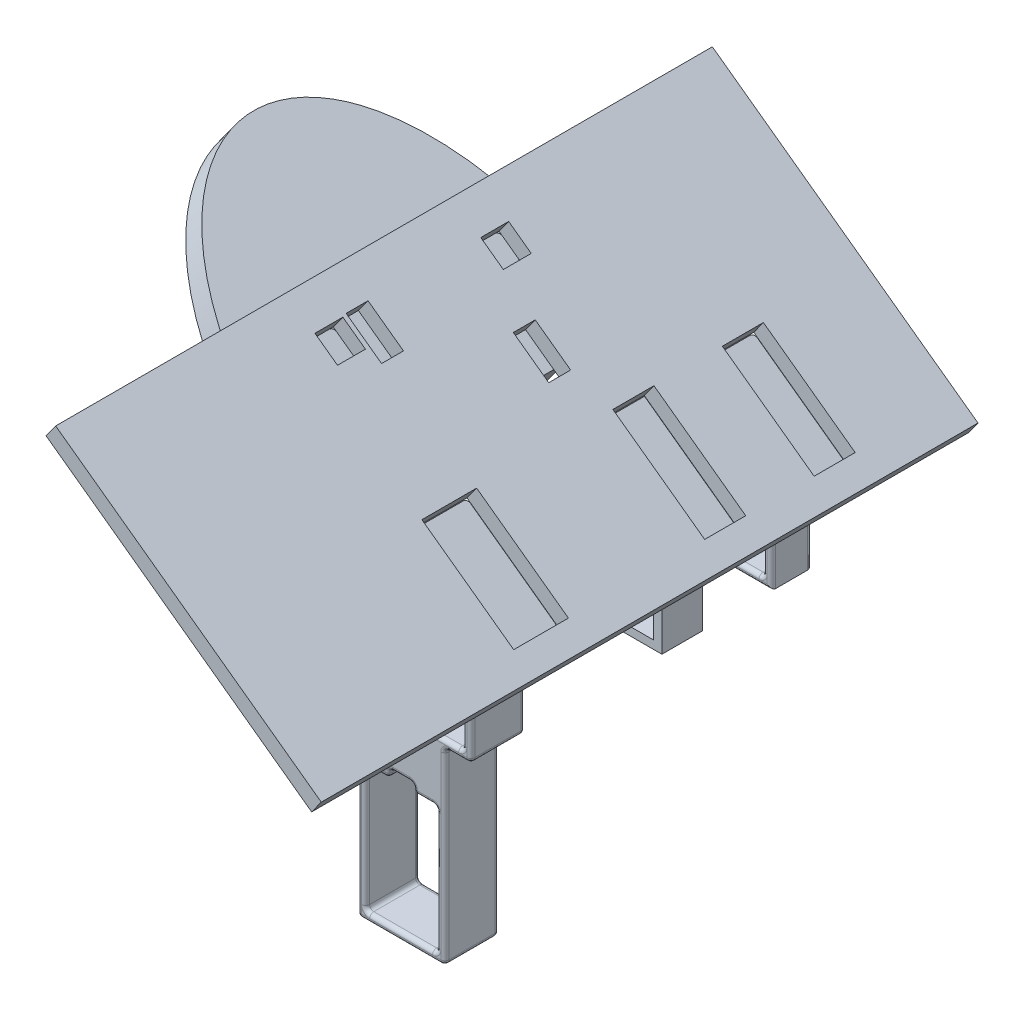
SolidWorks part; units mm, degrees
note: The reader was unsure of these and kept them because the rebuilt part matched: shared geometry of "Sketch7<2>".
ref_plane "Front Plane" through (0, 0, 0) normal (0, 0, 1) x (1, 0, 0)
ref_plane "Top Plane" through (0, 0, 0) normal (0, 1, 0) x (1, 0, 0)
ref_plane "Right Plane" through (0, 0, 0) normal (1, 0, 0) x (0, 0, -1)
sketch "Sketch3" plane through (0, 0, 0) normal (0, 0, 1) x (1, 0, 0)
  line L0 (-12.75, 5.65) -> (12.75, 5.65) construction
  line L1 (-11.25, -4.15) -> (11.25, -4.15)
  line L2 (-11.25, -4.15) -> (-11.25, 4.15)
  line L3 (-11.25, 4.15) -> (11.25, 4.15)
  line L4 (11.25, -4.15) -> (11.25, 4.15)
  line L5 (-11.25, -4.15) -> (11.25, 4.15) construction
  line L6 (-11.25, 4.15) -> (11.25, -4.15) construction
  line L7 (-6.5, -15.45) -> (6.5, -15.45) construction
  line L8 (-6.5, -15.45) -> (-6.5, -38.55)
  line L9 (-6.5, -38.55) -> (6.5, -38.55)
  line L10 (6.5, -15.45) -> (6.5, -38.55)
  line L11 (-6.5, -15.45) -> (6.5, -38.55) construction
  line L12 (-6.5, -38.55) -> (6.5, -15.45) construction
  line L13 (12.75, -5.65) -> (12.75, 5.65)
  line L15 (-12.75, -5.65) -> (-12.75, 5.65)
  line L16 (8, -13.95) -> (8, -40.05)
  line L17 (-8, -40.05) -> (8, -40.05)
  line L18 (-8, -13.95) -> (-8, -40.05)
  line L20 (-8, -13.95) -> (8, -13.95) construction
  line L21 (-12.75, -5.65) -> (12.75, -5.65) construction
  line L22 (-8, -13.95) -> (-8, -5.65)
  line L23 (-8, -5.65) -> (-12.75, -5.65)
  line L24 (12.75, -5.65) -> (8, -5.65)
  line L25 (8, -5.65) -> (8, -13.95)
  line L26 (-12.75, 5.65) -> (2.1671, 26.1817)
  line L27 (2.1671, 26.1817) -> (18.8571, 14.0557)
  line L28 (18.8571, 14.0557) -> (12.75, 5.65)
  line L29 (0, -40.05) -> (0, 5.65) construction
  line L30 (-6.5, -15.45) -> (-2.25, -15.45)
  line L31 (-2.25, -15.45) -> (-2.25, -13.95)
  line L32 (-2.25, -13.95) -> (2.25, -13.95)
  line L33 (2.25, -13.95) -> (2.25, -15.45)
  line L34 (2.25, -15.45) -> (6.5, -15.45)
  point P0 (0, 0)
  point P5 (0, -27)
  point P28 (0, -13.95)
  dimension "D1" = 22.5
  dimension "D2" = 1.5
  dimension "D3" = 27
  dimension "D4" = 13
  dimension "D5" = 23.1
  dimension "D7" = 1.5
  dimension "D8" = 54
  dimension "D9" = 10.39
  dimension "D10" = 8.4057
  dimension "D11" = 16
  dimension "D12" = 4.5
  dimension "D13" = 1.5
  dimension "D14" = 8.3
  dimension "D6" = 11.3
  dimension "D15" = 20.6299
extrude "Boss-Extrude1" add sketch "Sketch3" along normal blind 9.9
sketch "Sketch4" plane through (13.1988, 18.1666, 0) normal (0.5878, 0.809, 0) x (0.809, -0.5878, 0)
  line L0 (-3.321, 0) -> (-3.321, -9.9) construction
  line L1 (6.994, 0) -> (-13.636, 0) construction
  line L2 (6.994, -9.9) -> (-13.636, -9.9) construction
  line L3 (-13.636, -4.95) -> (6.994, -4.95) construction
  line L4 (-13.636, -9.9) -> (-13.636, 0) construction
  line L5 (6.994, -9.9) -> (6.994, 0) construction
  line L7 (-48.321, 71.1) -> (11.679, 71.1)
  line L8 (-48.321, 71.1) -> (-48.321, -48.9)
  line L9 (-48.321, -48.9) -> (11.679, -48.9)
  line L10 (11.679, 71.1) -> (11.679, -48.9)
  line L11 (-48.321, 71.1) -> (11.679, -48.9) construction
  line L12 (-48.321, -48.9) -> (11.679, 71.1) construction
  point P12 (-3.321, -4.95)
  point P13 (-18.321, 11.1)
  dimension "D1" = 120
  dimension "D2" = 60
  dimension "D3" = 16.05
  dimension "D4" = 15
extrude "Boss-Extrude2" add sketch "Sketch4" along normal blind 3
sketch "Sketch7" plane through (13.1988, 18.1666, 0) normal (-0.5878, -0.809, 0) x (0.809, -0.5878, 0)
  line L0 (-14.9179, -11.1) -> (-63.9179, -11.1) construction
  line L1 (-48.321, 48.9) -> (11.679, 48.9) construction
  line L6 (-36.7569, 1.65) -> (-41.8569, 1.65)
  line L7 (-36.7569, 1.65) -> (-36.7569, 6.75)
  line L8 (-36.7569, 6.75) -> (-41.8569, 6.75)
  line L9 (-41.8569, 1.65) -> (-41.8569, 6.75)
  line L10 (-36.7569, 1.65) -> (-41.8569, 6.75) construction
  line L11 (-36.7569, 6.75) -> (-41.8569, 1.65) construction
  line L12 (-48.321, -71.1) -> (-48.321, 48.9) construction
  line L13 (-36.7569, -23.55) -> (-36.7569, -28.65)
  line L14 (-36.7569, -23.55) -> (-41.8569, -23.55)
  line L15 (-41.8569, -23.55) -> (-41.8569, -28.65)
  line L16 (-36.7569, -28.65) -> (-41.8569, -28.65)
  line L17 (-41.8569, -23.55) -> (-36.7569, -28.65) construction
  point P10 (-39.3069, -26.1)
  point P11 (-39.3069, 4.2)
  point P12 (0, 0)
  point P13 (-36.7569, -28.65)
  point P18 (0, 0)
  point P19 (0, 0)
  point P20 (0, 0)
  point P21 (0, 0)
  dimension "D1" = 6.4641
  dimension "D3" = 5.1
  dimension "D4" = 5.1
  dimension "D5" = 5.1
  dimension "D6" = 6.4641
  dimension "D7" = 12.45
  dimension "D8" = 60
  dimension "D9" = 30.3
extrude "Boss-Extrude3" add sketch "Sketch7" along normal blind 4.5 and the other way blind 3
sketch "Sketch8" plane through (10.5538, 14.5261, 0) normal (-0.5878, -0.809, 0) x (0.809, -0.5878, 0)
  line L2 (-23.3069, 5.8504) -> (-23.3069, -28.0504)
  line L3 (-23.3069, 5.8504) -> (-34.6206, 17.1641)
  line L4 (-23.3069, -28.0504) -> (-34.6206, -39.3641)
  line L6 (11.679, -71.1) -> (-48.321, -71.1) construction
  line L7 (-48.321, 48.9) -> (11.679, -71.1) construction
  line L8 (-18.321, -11.1) -> (-48.321, -11.1) construction
  line L9 (11.679, 48.9) -> (11.679, -71.1) construction
  ellipse E0 centre (-23.3069, -11.1) end of major axis (-72.2778, -11.1) minor radius 29.05 (-34.6206, 17.1641) -> (-34.6206, -39.3641) ccw
  dimension "D1" = 4.9859
  dimension "D2" = 28.2641
  dimension "D3" = 23.9569
  dimension "D4" = 45
  dimension "D5" = 16
  dimension "D6" = 48.9709
  dimension "D7" = 60
  dimension "D8" = 34.9859
extrude "Boss-Extrude4" add sketch "Sketch8" along normal blind 5
ref_plane "Plane1" through (0, 0, -25) normal (0, 0, -1) x (-1, 0, 0)
ref_plane "Plane2" through (0, 0, -45) normal (0, 0, -1) x (-1, 0, 0)
sketch "Sketch9" plane through (0, 0, -25) normal (0, 0, -1) x (-1, 0, 0)
  line L0 (-20.6204, 16.4827) -> (-12.75, 5.65)
  line L2 (-3.9305, 28.6087) -> (12.75, 5.65)
  line L3 (12.75, 5.65) -> (12.75, -5.65)
  line L4 (12.75, -5.65) -> (8, -5.65)
  line L5 (8, -5.65) -> (-12.75, -5.65)
  line L6 (-12.75, -5.65) -> (-12.75, 5.65)
  line L7 (-11.25, 4.15) -> (11.25, 4.15)
  line L8 (11.25, 4.15) -> (11.25, -4.15)
  line L9 (11.25, -4.15) -> (-11.25, -4.15)
  line L10 (-11.25, -4.15) -> (-11.25, 4.15)
  line L12 (-24.4107, 13.7289) -> (-22.6474, 11.3019) construction
  line L13 (-24.4107, 13.7289) -> (24.1303, 48.9961) construction
  line L14 (-20.6204, 16.4827) -> (-3.9305, 28.6087)
  dimension "D1" = 4.685
extrude "Boss-Extrude5" add sketch "Sketch9" along normal blind 7.4 contours L10 L9 L8 L7 | L0 L6 L5 L4 L3 L2 L14
sketch "Sketch10" plane through (0, 0, -45) normal (0, 0, -1) x (-1, 0, 0)
  line L0 (-20.6204, 16.4827) -> (-12.75, 5.65)
  line L1 (-20.6204, 16.4827) -> (-3.9305, 28.6087)
  line L2 (-3.9305, 28.6087) -> (12.75, 5.65)
  line L3 (12.75, 5.65) -> (12.75, -5.65)
  line L6 (-12.75, -5.65) -> (-12.75, 5.65)
  line L7 (-11.25, 4.15) -> (11.25, 4.15)
  line L8 (11.25, 4.15) -> (11.25, -4.15)
  line L9 (11.25, -4.15) -> (-11.25, -4.15)
  line L10 (-11.25, -4.15) -> (-11.25, 4.15)
  line L11 (-24.4107, 13.7289) -> (24.1303, 48.9961) construction
  line L13 (-18.8571, 14.0557) -> (-12.75, 5.65) construction
  line L14 (-12.75, -5.65) -> (-12.75, 5.65) construction
  line L16 (-2.1671, 26.1817) -> (12.75, 5.65) construction
  line L17 (12.75, 5.65) -> (12.75, -5.65) construction
  line L18 (-12.75, -5.65) -> (12.75, -5.65)
extrude "Boss-Extrude6" add sketch "Sketch10" along normal blind 7.4
sketch "Sketch11" plane through (13.1988, 18.1666, 0) normal (-0.5878, -0.809, 0) x (0.809, -0.5878, 0)
  line L0 (-13.636, 9.9) -> (-13.636, 0) construction
  line L9 (6.994, 9.9) -> (6.994, 0) construction
  line L10 (-48.321, 48.9) -> (11.679, 48.9) construction
  line L11 (-13.636, -32.4) -> (-13.636, -25) construction
  line L12 (11.679, 48.9) -> (11.679, -71.1) construction
  line L13 (6.994, 9.9) -> (-13.636, 9.9) construction
  line L24 (-13.741, 9.95) -> (6.989, 9.95)
  line L25 (-13.741, 9.95) -> (-13.741, -0.05)
  line L26 (-13.741, -0.05) -> (6.989, -0.05)
  line L27 (6.989, 9.95) -> (6.989, -0.05)
  line L28 (-37.611, 48.9) -> (-37.611, -71.1) construction
  line L29 (6.994, 0) -> (-13.636, 0) construction
  line L30 (-13.741, -24.95) -> (6.989, -24.95)
  line L35 (-13.741, -24.95) -> (-13.741, -32.45)
  line L36 (-13.741, -32.45) -> (6.989, -32.45)
  line L37 (6.989, -24.95) -> (6.989, -32.45)
  line L38 (-13.636, -32.4) -> (6.994, -32.4) construction
  line L39 (6.994, -32.4) -> (6.994, -25) construction
  line L40 (-13.636, -25) -> (6.994, -25) construction
  line L42 (-13.741, -44.95) -> (6.989, -44.95)
  line L43 (-13.741, -44.95) -> (-13.741, -52.45)
  line L44 (-13.741, -52.45) -> (6.989, -52.45)
  line L45 (6.989, -44.95) -> (6.989, -52.45)
  line L46 (11.679, -71.1) -> (-48.321, -71.1) construction
  line L47 (-13.636, -45) -> (-13.636, -52.4) construction
  line L48 (-13.636, -52.4) -> (6.994, -52.4) construction
  point P20 (-37.611, -11.1)
  dimension "D2" = 38.95
  dimension "D3" = 4.69
  dimension "D4" = 20.73
  dimension "D5" = 20.73
  dimension "D6" = 7.5
  dimension "D7" = 4.69
  dimension "D8" = 20.73
  dimension "D9" = 4.69
  dimension "D10" = 7.5
  dimension "D11" = 73.85
  dimension "D12" = 18.65
  dimension "D13" = 10
  dimension "D14" = 0.105
  dimension "D15" = 0.005
  dimension "D16" = 0.05
  dimension "D17" = 0.05
  dimension "D18" = 0.105
  dimension "D19" = 0.05
  dimension "D20" = 0.005
  dimension "D21" = 0.05
  dimension "D22" = 0.105
  dimension "D23" = 0.05
  dimension "D24" = 13.85
  dimension "D25" = 33.85
extrude "Cut-Extrude4" cut sketch "Sketch7<2>" against normal blind 10
sketch "Sketch7<2>" plane through (13.1988, 18.1666, 0) normal (-0.5878, -0.809, 0) x (0.809, -0.5878, 0) same geometry as "Sketch7"
sketch "Sketch6" plane through (13.1988, 18.1666, 0) normal (-0.5878, -0.809, 0) x (0.809, -0.5878, 0)
  line L1 (-20.971, -23.075) -> (-28.971, -23.075)
  line L2 (-20.971, -23.075) -> (-20.971, -19.075)
  line L3 (-20.971, -19.075) -> (-28.971, -19.075)
  line L4 (-28.971, -23.075) -> (-28.971, -19.075)
  line L5 (-34.071, -3.125) -> (-42.071, -3.125)
  line L6 (-34.071, -3.125) -> (-34.071, 0.875)
  line L7 (-34.071, 0.875) -> (-42.071, 0.875)
  line L10 (-48.321, -71.1) -> (-48.321, 48.9) construction
  line L11 (-42.071, 0.875) -> (-42.071, -3.125)
  line L12 (-48.321, 48.9) -> (11.679, 48.9) construction
  dimension "D1" = 8
  dimension "D2" = 6.25
  dimension "D3" = 4
  dimension "D4" = 48.025
  dimension "D5" = 15.95
  dimension "D6" = 19.35
  dimension "D7" = 8
  dimension "D8" = 4
extrude "Cut-Extrude1" cut sketch "Sketch6" against normal up to surface (3 mm away) up to face at (-16.8378, 43.6977, 4.2)
fillet "Fillet1" radius 0.75 58 edges at (-11.25, 0, 9.9) (-11.25, 0, 0) (-10.375, -5.65, 9.9) (-10.375, -5.65, 0) (10.375, -5.65, 9.9) (10.375, -5.65, 0) (0, -38.55, 9.9) (0, -38.55, 0) (-6.5, -38.55, 4.95) (-6.5, -27, 9.9) (-6.5, -27, 0) (6.5, -27, 9.9) (6.5, -38.55, 4.95) (6.5, -27, 0) (0, -40.05, 9.9) (0, -40.05, 0) (8, -40.05, 4.95) (8, -22.85, 9.9) (8, -5.65, 4.95) (8, -22.85, 0) (12.75, -5.65, 4.95) (12.75, 0, 9.9) (12.75, 5.65, 4.95) (12.75, 0, 0) (-8, -5.65, 4.95) (-8, -22.85, 9.9) (-8, -40.05, 4.95) (-8, -22.85, 0) (-12.75, 5.65, 4.95) (-12.75, 0, 9.9) (-12.75, -5.65, 4.95) (-12.75, 0, 0) (11.25, 0, 9.9) (11.25, 0, 0) (-11.25, 4.15, 4.95) (0, 4.15, 9.9) (11.25, 4.15, 4.95) (0, 4.15, 0) (11.25, -4.15, 4.95) (0, -4.15, 9.9) (-11.25, -4.15, 4.95) (0, -4.15, 0) (15.8035, 9.8528, 9.9) (15.8035, 9.8528, 0) (-5.2914, 15.9158, 9.9) (-5.2914, 15.9158, 0) (-4.375, -15.45, 9.9) (-4.375, -15.45, 0) (4.375, -15.45, 9.9) (4.375, -15.45, 0) (-6.5, -15.45, 4.95) (6.5, -15.45, 4.95) (0, -13.95, 0) (-2.25, -15.45, 4.95) (-2.25, -13.95, 4.95) (0, -13.95, 9.9) (2.25, -13.95, 4.95) (2.25, -15.45, 4.95)
fillet "Fillet4" radius 0.75 25 edges at (12.75, 5.65, -48.7) (-12.75, 5.65, -48.7) (15.8035, 9.8528, -45) (12.75, 0, -45) (-12.75, 0, -45) (-5.2914, 15.9158, -45) (-11.25, 0, -45) (0, -4.15, -45) (11.25, 0, -45) (0, 4.15, -45) (-12.75, 0, -52.4) (12.75, 0, -52.4) (15.8035, 9.8528, -52.4) (-5.2914, 15.9158, -52.4) (0, -4.15, -52.4) (-11.25, 0, -52.4) (0, 4.15, -52.4) (11.25, 0, -52.4) (11.25, -4.15, -48.7) (-11.25, -4.15, -48.7) (11.25, 4.15, -48.7) (-11.25, 4.15, -48.7) (-12.75, -5.65, -48.7) (0, -5.65, -45) (0, -5.65, -52.4)
chamfer "Chamfer1" distance 2 angle 45 8 edges at (-21.2461, 37.6301, 1.65) (-19.1831, 36.1312, 4.2) (-21.2461, 37.6301, 6.75) (-23.3091, 39.1289, 4.2) (-21.2461, 37.6301, -23.55) (-19.1832, 36.1312, -26.1) (-21.2461, 37.6301, -28.65) (-23.3091, 39.1289, -26.1)
fillet "Fillet6" radius 0.75 8 edges at (-17.2728, 38.7605, 1.65) (-17.2728, 38.7605, 6.75) (-21.3988, 41.7582, 1.65) (-21.3988, 41.7582, 6.75) (-17.2728, 38.7605, -23.55) (-21.3988, 41.7582, -23.55) (-17.2728, 38.7605, -28.65) (-21.3988, 41.7582, -28.65)
extrude "Cut-Extrude5" cut sketch "Sketch11" against normal blind 10
